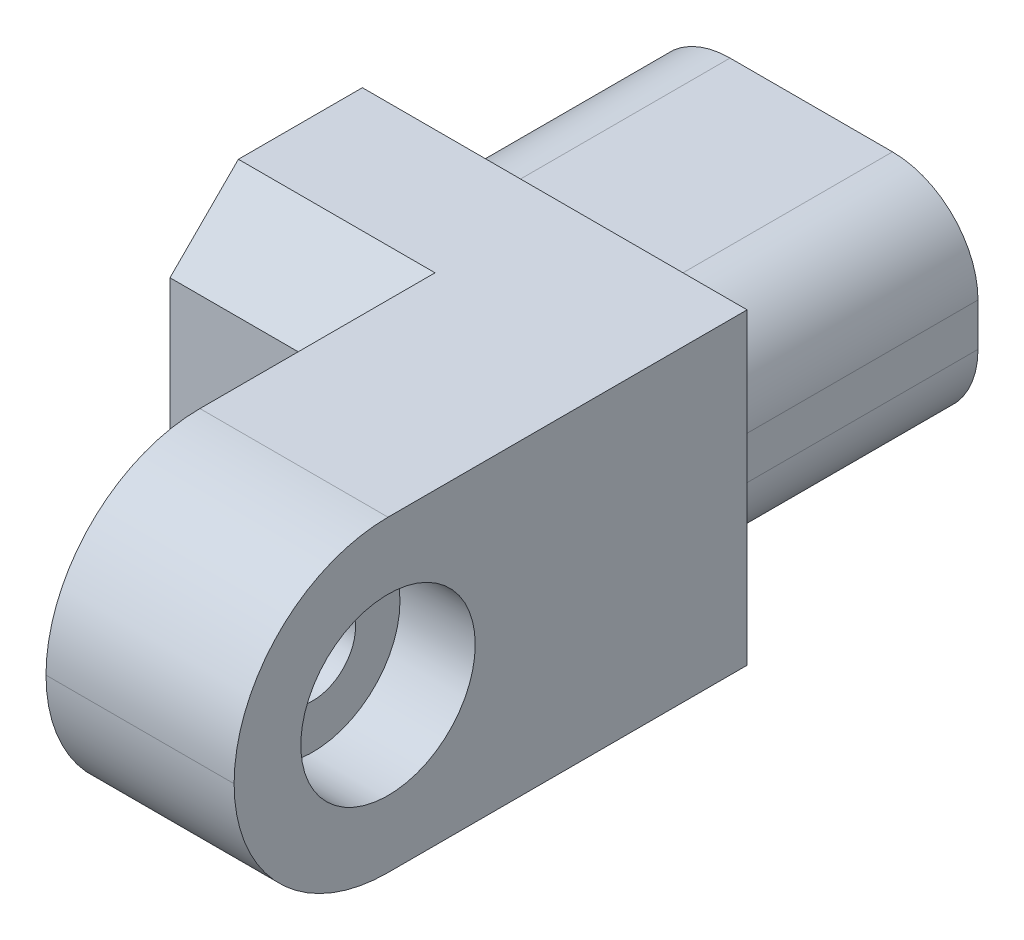
SolidWorks part; units mm, degrees
other "Markup1"
sketch "Sketch6" plane through (14.2875, 11.43, 38.1) normal (0.2973, 0.9472, 0.1204) x (0.8011, -0.1788, -0.5712)
ref_plane "Plan de face" through (0, 0, 0) normal (0, 0, 1) x (1, 0, 0)
ref_plane "Plan de dessus" through (0, 0, 0) normal (0, 1, 0) x (1, 0, 0)
ref_plane "Plan de droite" through (0, 0, 0) normal (1, 0, 0) x (0, 0, -1)
sketch "Sketch2" plane through (0, 0, 0) normal (0, 0, 1) x (1, 0, 0)
  line L1 (12.3825, -7.9375) -> (-12.3825, -7.9375)
  line L2 (12.3825, -7.9375) -> (12.3825, 7.9375)
  line L3 (12.3825, 7.9375) -> (-12.3825, 7.9375)
  line L4 (-12.3825, -7.9375) -> (-12.3825, 7.9375)
  line L5 (12.3825, -7.9375) -> (-12.3825, 7.9375) construction
  line L6 (12.3825, 7.9375) -> (-12.3825, -7.9375) construction
  point P0 (0, 0)
  dimension "D1" = 24.765
  dimension "D2" = 15.875
extrude "Boss-Extrude1" add sketch "Sketch2" against normal blind 19.05
sketch "Sketch3" plane through (0, 0, 0) normal (0, 0, 1) x (1, 0, 0)
  line L1 (14.2875, -11.43) -> (-14.2875, -11.43)
  line L2 (14.2875, -11.43) -> (14.2875, 11.43)
  line L3 (14.2875, 11.43) -> (-14.2875, 11.43)
  line L4 (-14.2875, -11.43) -> (-14.2875, 11.43)
  line L5 (14.2875, -11.43) -> (-14.2875, 11.43) construction
  line L6 (14.2875, 11.43) -> (-14.2875, -11.43) construction
  point P0 (0, 0)
  dimension "D1" = 28.575
  dimension "D2" = 22.86
extrude "Boss-Extrude2" add sketch "Sketch3" along normal blind 38.1
sketch "Sketch4" plane through (0, -11.43, 0) normal (0, -1, 0) x (-1, 0, 0)
  line L0 (14.2875, -38.1) -> (-14.2875, -38.1) construction
  line L5 (14.2875, -38.1) -> (-0.3175, -38.1)
  line L6 (14.2875, -38.1) -> (14.2875, -14.2875)
  line L7 (14.2875, -14.2875) -> (-0.3175, -14.2875)
  line L8 (-0.3175, -38.1) -> (-0.3175, -14.2875)
  line L9 (-14.2875, -38.1) -> (-14.2875, 0) construction
  line L10 (14.2875, -38.1) -> (14.2875, 0) construction
  dimension "D2" = 23.8125
  dimension "D5" = 13.97
extrude "Cut-Extrude1" cut sketch "Sketch4" against normal through all
fillet "Fillet5" radius 11.43 2 edges at (7.3025, -11.43, 38.1) (7.3025, 11.43, 38.1)
fillet "Fillet3" radius 6.35 4 edges at (-12.3825, -7.9375, -9.525) (-12.3825, 7.9375, -9.525) (12.3825, -7.9375, -9.525) (12.3825, 7.9375, -9.525)
chamfer "Chamfer1" distance 5.08 angle 45 2 edges at (-6.985, -11.43, 14.2875) (-6.985, 11.43, 14.2875)
hole_wizard "CBORE for 1/4 Fillister Head Machine Screw1" positions "3DSketch1" profile "Sketch5" counterbore size "1/4" standard "ANSI Inch" end condition up to next
sketch3d "3DSketch1"
  point P0 (14.2875, 0, 26.67)
  point P6 (14.2875, 0, 34.6604)
  point P7 (14.2875, 0, 27.1011)
  point P8 (0, 0, 0)
  point P9 (14.2875, 0, 27.1368)
sketch "Sketch5" plane through (14.2875, 0, 26.67) normal (0, 1, 0) x (0, 0, -1)
  line L0 (0, 0) -> (0, 13.97)
  line L1 (0, 13.97) -> (3.175, 13.97)
  line L3 (3.175, 13.97) -> (3.175, 5.588)
  line L4 (3.175, 5.588) -> (6.477, 5.588)
  line L5 (6.477, 5.588) -> (6.477, 0)
  line L7 (6.477, 0) -> (0, 0)
  line L11 (0, -6.35) -> (0, 107.95) construction
  dimension "Thru Hole Dia." = 6.35
  dimension "Thru Hole Depth" = 13.97
  dimension "C'Bore Dia." = 12.954
  dimension "C'Bore Depth" = 5.588
ref_plane "Plane1" through (6.985, 0, 0) normal (1, 0, 0) x (0, 0, -1)
mirror "Mirror1" about plane through (6.985, 0, 0) normal (1, 0, 0) of "CBORE for 1/4 Fillister Head Machine Screw1"
